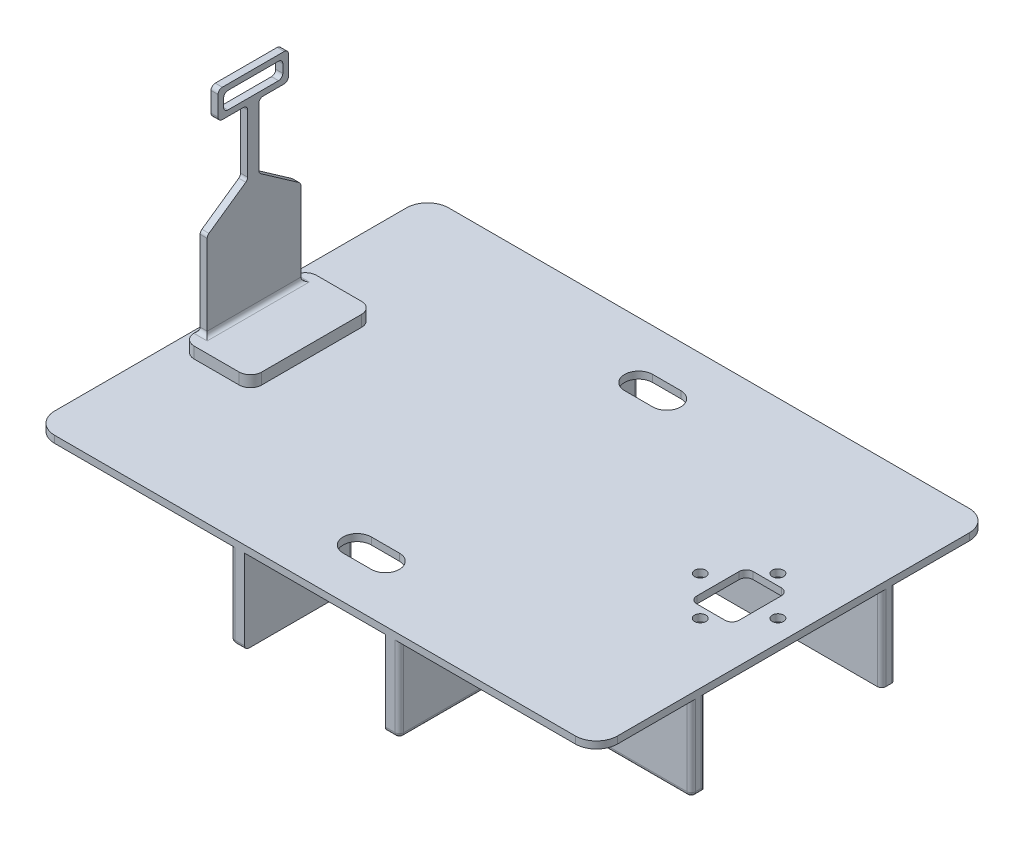
SolidWorks part; units mm, degrees
ref_plane "Front Plane" through (0, 0, 0) normal (0, 0, 1) x (1, 0, 0)
ref_plane "Top Plane" through (0, 0, 0) normal (0, 1, 0) x (1, 0, 0)
ref_plane "Right Plane" through (0, 0, 0) normal (1, 0, 0) x (0, 0, -1)
sketch "Sketch1" plane through (0, 0, 0) normal (0, 1, 0) x (1, 0, 0)
  line L1 (254, -177.8) -> (-254, -177.8)
  line L2 (254, -177.8) -> (254, 177.8)
  line L3 (254, 177.8) -> (-254, 177.8)
  line L4 (-254, -177.8) -> (-254, 177.8)
  line L5 (254, -177.8) -> (-254, 177.8) construction
  line L6 (254, 177.8) -> (-254, -177.8) construction
  point P0 (0, 0)
  dimension "D1" = 508
  dimension "D2" = 355.6
extrude "Boss-Extrude1" add sketch "Sketch1" along normal blind 6.35
sketch "Sketch2" plane through (0, 6.35, 0) normal (0, 1, 0) x (1, 0, 0)
  line L0 (-12.7, -127) -> (12.7, -127) construction
  line L1 (-12.7, -114.3) -> (12.7, -114.3)
  line L2 (-12.7, -139.7) -> (12.7, -139.7)
  line L3 (-54.7425, 0) -> (78.2767, 0) construction
  line L4 (-12.7, 127) -> (12.7, 127) construction
  line L5 (-12.7, 114.3) -> (12.7, 114.3)
  line L6 (-12.7, 139.7) -> (12.7, 139.7)
  line L8 (212.09, -19.8474) -> (186.69, -19.8474)
  line L9 (218.44, -13.4974) -> (218.44, 24.6026)
  line L10 (212.09, 30.9526) -> (186.69, 30.9526)
  line L11 (180.34, -13.4974) -> (180.34, 24.6026)
  line L12 (218.44, -19.8474) -> (180.34, 30.9526) construction
  line L13 (218.44, 30.9526) -> (180.34, -19.8474) construction
  arc A0 (-12.7, -114.3) -> (-12.7, -139.7) centre (-12.7, -127) ccw
  arc A1 (12.7, -139.7) -> (12.7, -114.3) centre (12.7, -127) ccw
  arc A2 (-12.7, 114.3) -> (-12.7, 139.7) centre (-12.7, 127) cw
  arc A3 (12.7, 139.7) -> (12.7, 114.3) centre (12.7, 127) cw
  arc A4 (186.69, -19.8474) -> (180.34, -13.4974) centre (186.69, -13.4974) cw
  arc A5 (212.09, -19.8474) -> (218.44, -13.4974) centre (212.09, -13.4974) ccw
  arc A6 (218.44, 24.6026) -> (212.09, 30.9526) centre (212.09, 24.6026) ccw
  arc A7 (186.69, 30.9526) -> (180.34, 24.6026) centre (186.69, 24.6026) ccw
  circle A8 centre (234.442, 5.5526) radius 5.08
  circle A9 centre (199.39, -29.4994) radius 5.08
  circle A10 centre (164.338, 5.5526) radius 5.08
  circle A11 centre (199.39, 40.6046) radius 5.08
  point P2 (0, -127)
  point P13 (0, 127)
  point P18 (199.39, 5.5526)
  point P45 (199.39, 5.5526)
  dimension "D2" = 12.7
  dimension "D7" = 6.35
  dimension "D8" = 10.16
  dimension "D1" = 25.4
  dimension "D3" = 127
  dimension "D4" = 50.8
  dimension "D5" = 38.1
  dimension "D6" = 199.39
  dimension "D9" = 35.052
  dimension "D10" = 4
extrude "Cut-Extrude1" cut sketch "Sketch2" against normal blind 38.1
fillet "Fillet1" radius 19.05 4 edges at (-254, 3.175, -177.8) (254, 3.175, -177.8) (254, 3.175, 177.8) (-254, 3.175, 177.8)
sketch "Sketch3" plane through (0, 6.35, 0) normal (0, 1, 0) x (1, 0, 0)
  line L1 (-191.008, -55.245) -> (-231.648, -55.245)
  line L2 (-180.848, -45.085) -> (-180.848, 45.085)
  line L3 (-191.008, 55.245) -> (-231.648, 55.245)
  line L4 (-241.808, -45.085) -> (-241.808, 45.085)
  line L5 (-180.848, -55.245) -> (-241.808, 55.245) construction
  line L6 (-180.848, 55.245) -> (-241.808, -55.245) construction
  arc A0 (-191.008, -55.245) -> (-180.848, -45.085) centre (-191.008, -45.085) ccw
  arc A1 (-231.648, -55.245) -> (-241.808, -45.085) centre (-231.648, -45.085) cw
  arc A2 (-180.848, 45.085) -> (-191.008, 55.245) centre (-191.008, 45.085) ccw
  arc A3 (-231.648, 55.245) -> (-241.808, 45.085) centre (-231.648, 45.085) ccw
  point P0 (-211.328, 0)
  point P18 (0, 0)
  dimension "D4" = 10.16
  dimension "D1" = 60.96
  dimension "D2" = 110.49
  dimension "D3" = 211.328
extrude "Boss-Extrude2" add sketch "Sketch3" along normal blind 10.16
sketch "Sketch5" plane through (0, 16.51, 0) normal (0, 1, 0) x (1, 0, 0)
  line L0 (-241.808, 0.6995) -> (-180.848, 0) construction
  line L1 (-233.553, -41.5915) -> (-239.903, -41.5915)
  line L2 (-233.553, -41.5915) -> (-233.553, 42.9905)
  line L3 (-233.553, 42.9905) -> (-239.903, 42.9905)
  line L4 (-239.903, -41.5915) -> (-239.903, 42.9905)
  line L5 (-233.553, -41.5915) -> (-239.903, 42.9905) construction
  line L6 (-233.553, 42.9905) -> (-239.903, -41.5915) construction
  line L7 (-241.808, 45.085) -> (-241.808, -45.085) construction
  line L8 (-180.848, -45.085) -> (-180.848, 45.085) construction
  point P0 (-236.728, 0.6995)
  point P11 (-211.328, 0.3498)
  point P12 (0, 0)
  dimension "D1" = 84.582
  dimension "D2" = 6.35
  dimension "D3" = 25.4
extrude "Boss-Extrude3" add sketch "Sketch5" along normal blind 203.2
fillet "Fillet4" radius 3.81 3 edges at (-236.728, 16.51, -42.9905) (-236.728, 16.51, 41.5915) (-233.553, 16.51, -0.6995)
fillet "Fillet5" radius 3.81 1 edges at (-239.903, 16.51, -0.6995)
sketch "Sketch8" plane through (-239.903, 0, 0) normal (-1, 0, 0) x (0, 0, 1)
  line L0 (0, 191.5219) -> (0, 0) construction
  line L1 (31.75, 178.8219) -> (-31.75, 178.8219)
  line L2 (31.75, 178.8219) -> (31.75, 204.2219)
  line L3 (31.75, 204.2219) -> (-31.75, 204.2219)
  line L4 (-31.75, 178.8219) -> (-31.75, 204.2219)
  line L5 (31.75, 178.8219) -> (-31.75, 204.2219) construction
  line L6 (31.75, 204.2219) -> (-31.75, 178.8219) construction
  line L7 (-5.08, 178.8219) -> (-5.08, 120.4484)
  line L8 (-5.08, 120.4484) -> (-42.9905, 93.9032)
  line L9 (-42.9905, 219.71) -> (-42.9905, 20.32) construction
  line L10 (-42.9905, 93.9032) -> (-42.9905, 35.4832)
  line L11 (-42.9905, 35.4832) -> (42.9905, 35.4832)
  line L12 (42.9905, 93.9032) -> (42.9905, 35.4832)
  line L13 (5.08, 120.4484) -> (42.9905, 93.9032)
  line L14 (5.08, 178.8219) -> (5.08, 120.4484)
  line L15 (26.67, 199.1419) -> (-26.67, 199.1419)
  line L16 (-26.67, 183.9019) -> (-26.67, 199.1419)
  line L17 (26.67, 183.9019) -> (-26.67, 183.9019)
  line L18 (26.67, 183.9019) -> (26.67, 199.1419)
  line L19 (-43.0249, 19.8096) -> (41.6258, 19.8096) construction
  point P0 (0, 191.5219)
  point P16 (0, 35.4832)
  line M13 (41.5915, 20.32) -> (41.5915, 219.71)
  line M14 (41.5915, 219.71) -> (-42.9905, 219.71)
  line M15 (-42.9905, 219.71) -> (-42.9905, 20.32)
  dimension "D1" = 25.4
  dimension "D2" = 63.5
  dimension "D3" = 10.16
  dimension "D4" = 58.42
  dimension "D5" = 55
  dimension "D7" = 15.6736
  dimension "D8" = 159.0124
  dimension "D6" = 5.08
extrude "Cut-Extrude3" cut sketch "Sketch8" against normal blind 97.028 contours L1 L14 L13 L8 L7 L4 L3 L2 M13 M14 M15 | L17 L18 L15 L16 region at (-239.903, 191.5219, 33.266) region at (-239.903, 191.5219, 0)
fillet "Fillet6" radius 3.81 14 edges at (-236.728, 94.8828, 41.5915) (-236.728, 120.4484, 5.08) (-236.728, 93.9032, -42.9905) (-236.728, 120.4484, -5.08) (-236.728, 178.8219, -5.08) (-236.728, 178.8219, -31.75) (-236.728, 204.2219, -31.75) (-236.728, 183.9019, 26.67) (-236.728, 199.1419, 26.67) (-236.728, 199.1419, -26.67) (-236.728, 178.8219, 5.08) (-236.728, 183.9019, -26.67) (-236.728, 178.8219, 31.75) (-236.728, 204.2219, 31.75)
sketch "Sketch9" plane through (0, 0, 0) normal (0, -1, 0) x (1, 0, 0)
  line L0 (-254, 92.2557) -> (-76.2, 92.2557)
  line L1 (-254, -158.75) -> (-254, 158.75) construction
  line L2 (-76.2, 92.2557) -> (-76.2, 177.8)
  line L3 (-234.95, 177.8) -> (234.95, 177.8) construction
  line L4 (-254, 79.5557) -> (-63.5, 79.5557)
  line L5 (-63.5, 79.5557) -> (-63.5, 177.8)
  line L6 (-254, 92.2557) -> (-254, 79.5557)
  line L7 (-76.2, 177.8) -> (-63.5, 177.8)
  dimension "D1" = 177.8
  dimension "D2" = 12.7
  dimension "D3" = 12.7
extrude "Boss-Extrude4" add sketch "Sketch9" along normal blind 76.2
fillet "Fillet7" radius 3.81 5 edges at (-76.2, -38.1, 92.2557) (-69.85, -76.2, 177.8) (-254, -76.2, 85.9057) (-254, -38.1, 79.5557) (-63.5, -38.1, 79.5557)
mirror "Mirror1" about plane through (0, 0, 0) normal (0, 0, 1) of "Boss-Extrude4"
fillet "Fillet8" radius 3.81 14 edges at (-76.2, -36.195, 177.8) (-76.2, -75.0841, 176.6841) (-76.2, -76.2, 135.0279) (-77.3159, -76.2, 93.3717) (-165.1, -76.2, 92.2557) (-252.8841, -75.0841, 92.2557) (-254, -36.195, 92.2557) (-76.2, -38.1, -92.2557) (-76.2, -38.1, -177.8) (-254, -38.1, -92.2557) (-254, -38.1, -79.5557) (-63.5, -38.1, -177.8) (-69.85, -76.2, -177.8) (-63.5, -38.1, -79.5557)
mirror "Mirror2" about plane through (0, 0, 0) normal (1, 0, 0) of "Fillet8", "Mirror1", "Fillet7", "Boss-Extrude4"
